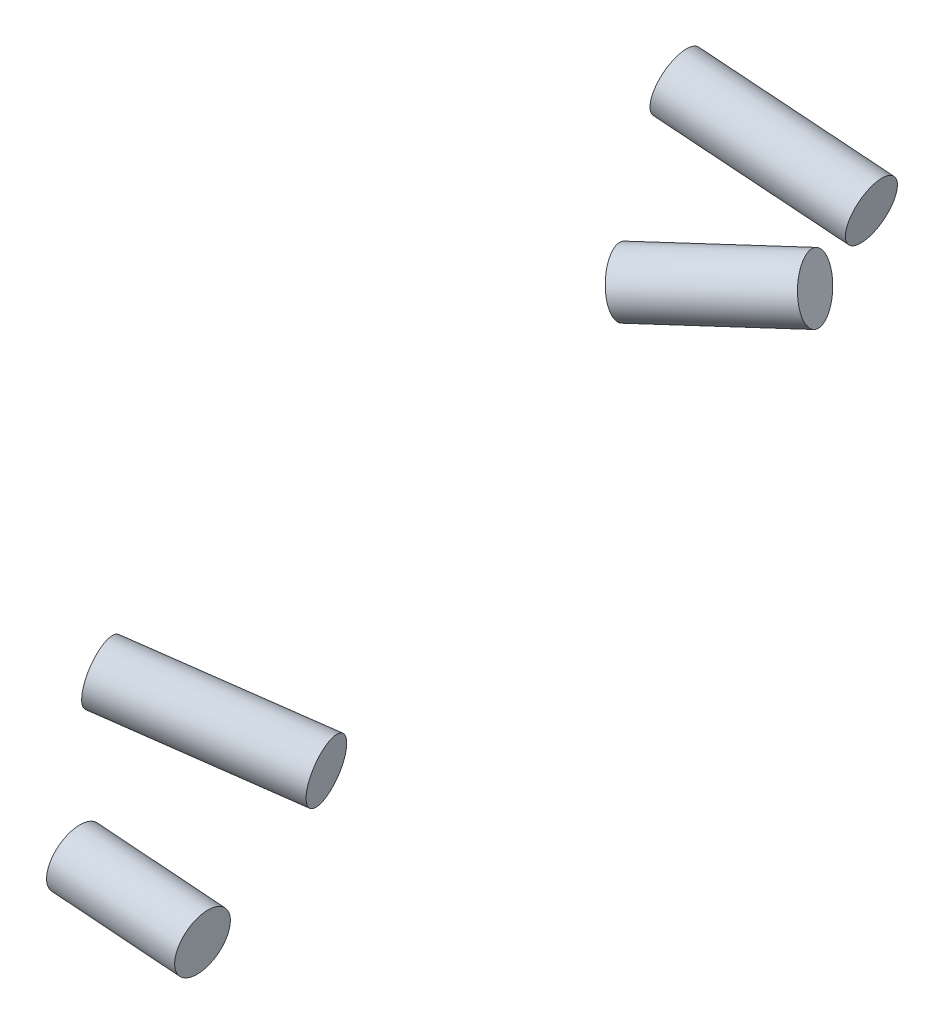
SolidWorks part; units mm, degrees
ref_plane "Plano frontal" through (0, 0, 0) normal (0, 0, 1) x (1, 0, 0)
ref_plane "Plano superior" through (0, 0, 0) normal (0, 1, 0) x (1, 0, 0)
ref_plane "Plano direito" through (0, 0, 0) normal (1, 0, 0) x (0, 0, -1)
sketch3d "SUSP_FR_rocker_bracket_a_eixo"
  line L0 (258.3043, 43.4709, -246.6084) -> (300.1526, 37.6935, -258.7919)
sweep "SUSP_FR_rocker_bracket_a" add path "SUSP_FR_rocker_bracket_a_eixo" circular profile diameter 14 parameters "D3"=14
sketch3d "SUSP_FR_rocker_bracket_b_eixo"
  line L0 (253.1609, 3.0606, -245.1125) -> (282.5474, -0.7335, -246.5681)
sweep "SUSP_FR_rocker_bracket_b" add path "SUSP_FR_rocker_bracket_b_eixo" circular profile diameter 14 parameters "D3"=14
sketch3d "SUSP_FR_coilover_bracket_a_eixo"
  line L0 (164.8059, 4.0474, -478.3248) -> (206.5598, -4.6958, -483.6357)
sweep "SUSP_FR_coilover_bracket_a" add path "SUSP_FR_coilover_bracket_a_eixo" circular profile diameter 14 parameters "D3"=14
sketch3d "SUSP_FR_coilover_bracket_b_eixo"
  line L0 (166.0262, -30.2321, -464.3188) -> (198.5574, -22.1626, -478.0795)
sweep "SUSP_FR_coilover_bracket_b" add path "SUSP_FR_coilover_bracket_b_eixo" circular profile diameter 14 parameters "D3"=14
sketch3d "REF_SKETCH"
  line L0 (251, -223.87, -256.303) -> (259, -219.07, -252.703)
  line L1 (257.4, -224.47, -257.703) -> (252.6, -218.47, -251.303)
  line L2 (255, -221.47, -254.503) -> (255, -14.5, -244.753)
  line L3 (201, -243.24, -44.183) -> (209, -238.44, -40.583)
  line L4 (207.4, -243.84, -45.583) -> (202.6, -237.84, -39.183)
  line L5 (205, -240.84, -42.383) -> (205, 0, -42.383)
  line L6 (266, -92.8, -84.1915) -> (274, -88, -80.5915)
  line L7 (272.4, -93.4, -85.5915) -> (267.6, -87.4, -79.1915)
  line L8 (287.35, 16.08, -254.48) -> (295.35, 20.88, -250.88)
  line L9 (293.75, 15.48, -255.88) -> (288.95, 21.48, -249.48)
  line L10 (279.3464, -7.7202, -244.3456) -> (303.3536, 44.6802, -261.0144)
  line L11 (198.5586, -15.8292, -482.6576) -> (206.5586, -11.0292, -479.0576)
  line L12 (204.9586, -16.4292, -484.0576) -> (200.1586, -10.4292, -477.6576)
ref_point "P_UCA_IN_FRONT"
ref_axis "A_UCA_PIVOT" through (255, -221.47, -254.503) along (0, 0.9989, 0.0471)
ref_point "P_LCA_IN_FRONT"
ref_axis "A_LCA_PIVOT" through (205, -240.84, -42.383) along (0, 1, 0)
ref_point "P_TIE_ROD_IN"
ref_point "P_ROCKER_PIVOT"
ref_axis "A_ROCKER" through (279.3464, -7.7202, -244.3456) along (0.4001, 0.8733, -0.2778)
ref_point "P_DAMPER_CHASSIS"
